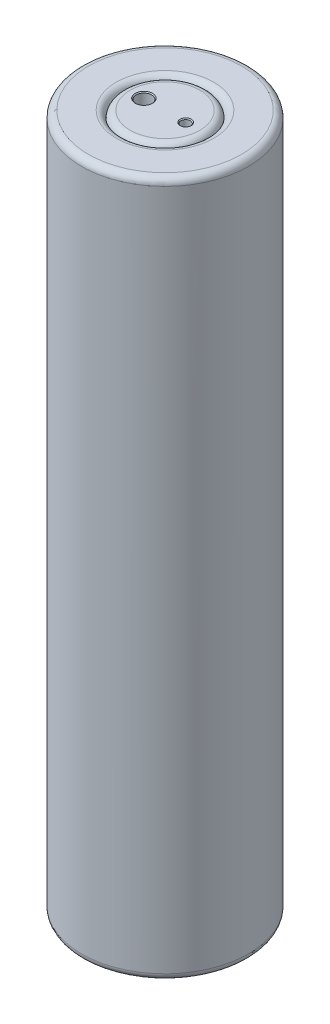
SolidWorks part; units mm, degrees
ref_plane "Plan de face" through (0, 0, 0) normal (0, 0, 1) x (1, 0, 0)
ref_plane "Plan de dessus" through (0, 0, 0) normal (0, 1, 0) x (1, 0, 0)
ref_plane "Plan de droite" through (0, 0, 0) normal (1, 0, 0) x (0, 0, -1)
sketch "Esquisse2" plane through (0, 0, 0) normal (1, 0, 0) x (0, 0, -1)
  line L0 (12.834, -467.6677) -> (12.834, -477.6677)
  line L1 (-17.166, 22.3323) -> (12.834, 22.3323)
  line L2 (-17.166, 22.3323) -> (-17.166, -477.6677)
  line L3 (-17.166, -477.6677) -> (12.834, -477.6677)
  line L4 (12.834, 22.3323) -> (12.834, 12.3323)
  line L5 (12.834, 12.3323) -> (-13.166, 12.3323)
  line L7 (12.834, -467.6677) -> (-13.166, -467.6677)
  line L8 (-13.166, 12.3323) -> (-13.166, -467.6677)
  dimension "D1" = 30
  dimension "D2" = 500
  dimension "D3" = 10
  dimension "D4" = 10
  dimension "D5" = 4
revolve "Révolution1" add sketch "Esquisse2" angle 360 about L0
fillet "Congé1" radius 5 1 edges at (0, 22.3323, 17.166)
fillet "Congé2" radius 5 1 edges at (0, -477.6677, 17.166)
sketch "Esquisse3" plane through (0, 0, 0) normal (1, 0, 0) x (0, 0, -1)
  line L0 (37.834, 22.3323) -> (-12.166, 22.3323) construction
  line L1 (-47.166, 22.3323) -> (-17.166, 22.3323)
  line L2 (-47.166, 22.3323) -> (-47.166, -477.6677)
  line L3 (-47.166, -477.6677) -> (-17.166, -477.6677)
  line L4 (-17.166, 22.3323) -> (-17.166, -477.6677)
  line L5 (-17.166, 17.3323) -> (-17.166, -472.6677) construction
  line L6 (42.834, -472.6677) -> (42.834, 17.3323) construction
  line L8 (-43.166, 12.3323) -> (-21.166, 12.3323)
  line L9 (-43.166, 12.3323) -> (-43.166, -467.6677)
  line L10 (-43.166, -467.6677) -> (-21.166, -467.6677)
  line L11 (-21.166, 12.3323) -> (-21.166, -467.6677)
  dimension "D1" = 500
  dimension "D2" = 0
  dimension "D3" = 0
  dimension "D4" = 90
  dimension "D5" = 10
  dimension "D6" = 4
  dimension "D7" = 4
  dimension "D8" = 10
ref_axis "Axe1" through (0, -472.6677, -12.834) along (0, 1, 0)
revolve "Révolution2" add sketch "Esquisse3" angle 360 about axis through (0, -472.6677, -12.834) along (0, 1, 0)
fillet "Congé3" radius 5 2 edges at (0, 22.3323, -72.834) (0, 22.3323, -42.834)
fillet "Congé4" radius 5 2 edges at (0, -477.6677, -42.834) (0, -477.6677, -72.834)
sketch "Esquisse4" plane through (0, 22.3323, 0) normal (0, 1, 0) x (1, 0, 0)
  point P0 (-14.999, 12.6567)
  point P1 (14.9991, 12.6666)
  dimension "D1" = 15
  dimension "D2" = 15
hole_wizard "Perçage pour tuyau pour trou taraudé 1/41" positions "Esquisse3D1" profile "Esquisse5" hole size "1/4" standard "Ansi Inch" end condition up to next
sketch3d "Esquisse3D1"
  point P0 (-14.999, 22.3323, -12.6567)
sketch "Esquisse5" plane through (-14.999, 22.3323, -12.6567) normal (1, 0, 0) x (0, 0, 1)
  line L0 (0, 0) -> (0, 10)
  line L1 (0, 10) -> (5.5626, 10)
  line L2 (5.5626, 10) -> (5.5626, 0.635)
  line L3 (5.5626, 0.635) -> (6.1976, 0)
  line L5 (6.1976, 0) -> (0, 0)
  line L6 (-5.5626, 0.635) -> (-6.1976, 0) construction
  line L11 (0, -6.35) -> (0, 107.95) construction
  dimension "Diamètre du perçage jusqu'au prochain" = 11.1252
  dimension "Profondeur du perçage jusqu'au prochain" = 10
  dimension "Diamètre du fraisage entrant" = 12.3952
  dimension "Angle du fraisage entrant" = 90
hole_wizard "Dégagement 1/41" positions "Esquisse3D2" profile "Esquisse6" hole size "1/4" standard "Ansi Inch" end condition up to next
sketch3d "Esquisse3D2"
  point P0 (14.9991, 22.3323, -12.6666)
sketch "Esquisse6" plane through (14.9991, 22.3323, -12.6666) normal (1, 0, 0) x (0, 0, 1)
  line L0 (0, 0) -> (0, 10)
  line L1 (0, 10) -> (3.3782, 10)
  line L2 (3.3782, 10) -> (3.3782, 0.635)
  line L3 (3.3782, 0.635) -> (4.0132, 0)
  line L5 (4.0132, 0) -> (0, 0)
  line L6 (-3.3782, 0.635) -> (-4.0132, 0) construction
  line L11 (0, -6.35) -> (0, 107.95) construction
  dimension "Diamètre du perçage jusqu'au prochain" = 6.7564
  dimension "Profondeur du perçage jusqu'au prochain" = 10
  dimension "Diamètre du fraisage entrant" = 8.0264
  dimension "Angle du fraisage entrant" = 90
sketch "Esquisse8" plane through (0, -477.6677, 0) normal (0, -1, 0) x (1, 0, 0)
  point P0 (-44.9995, -13.042)
  point P1 (59.9994, -13.1124)
  point P3 (-69.9997, -13.0381)
  dimension "D1" = 45
  dimension "D2" = 60
  dimension "D3" = 70
hole_wizard "Dégagement 1/21" positions "Esquisse3D4" profile "Esquisse10" hole size "1/2" standard "Ansi Inch" end condition up to next
sketch3d "Esquisse3D4"
  point P0 (-44.9995, -477.6677, -13.042)
sketch "Esquisse10" plane through (-44.9995, -477.6677, -13.042) normal (1, 0, 0) x (0, 0, -1)
  line L0 (0, 0) -> (0, 10)
  line L1 (0, 10) -> (6.7462, 10)
  line L2 (6.7462, 10) -> (6.7462, 0.635)
  line L3 (6.7462, 0.635) -> (7.3812, 0)
  line L5 (7.3812, 0) -> (0, 0)
  line L6 (-6.7462, 0.635) -> (-7.3812, 0) construction
  line L11 (0, -6.35) -> (0, 107.95) construction
  dimension "Diamètre du perçage jusqu'au prochain" = 13.4925
  dimension "Profondeur du perçage jusqu'au prochain" = 10
  dimension "Diamètre du fraisage entrant" = 14.7625
  dimension "Angle du fraisage entrant" = 90
